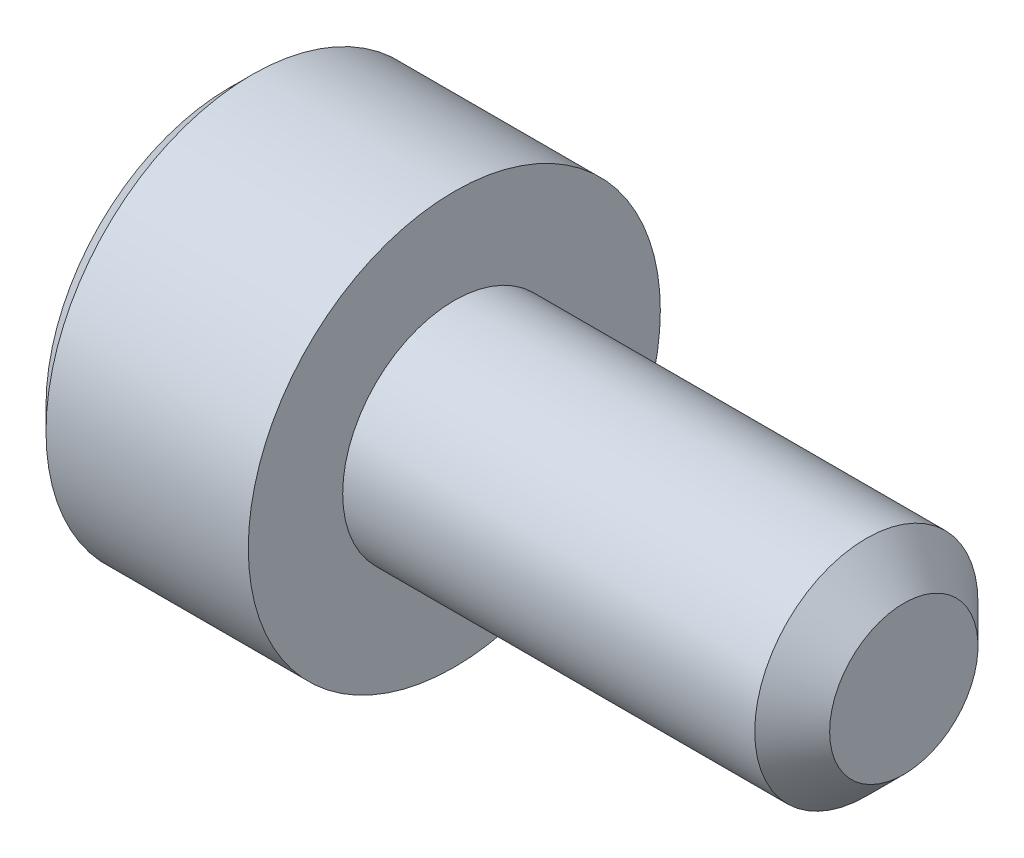
SolidWorks part; units mm, degrees
material "AISI Type 316L stainless steel"
ref_plane "Front Plane" through (0, 0, 0) normal (0, 0, 1) x (1, 0, 0)
ref_plane "Top Plane" through (0, 0, 0) normal (0, 1, 0) x (1, 0, 0)
ref_plane "Right Plane" through (0, 0, 0) normal (1, 0, 0) x (0, 0, -1)
sketch "Sketch1" plane through (0, 0, 0) normal (0, 0, 1) x (1, 0, 0)
  line L0 (-88.7055, 0) -> (96.9812, 0) construction
  line L1 (0, 0) -> (0, 2.75)
  line L2 (0, 2.75) -> (3, 2.75)
  line L4 (9, 0) -> (9, 1.49)
  line L5 (9, 1.49) -> (3, 1.49)
  line L6 (3, 1.49) -> (3, 2.75)
  line L7 (0, 0) -> (9, 0)
  dimension "D1" = 6
  dimension "D2" = 3
  dimension "D3" = 2.75
  dimension "D4" = 1.49
revolve "Revolve1" add sketch "Sketch1" angle 360 about L0
chamfer "Chamfer1" distance 0.5 angle 45 1 edges at (9, 0, 1.49)
chamfer "Chamfer2" distance 0.3 angle 45 1 edges at (0, 0, 2.75)
sketch "Sketch3" plane through (0, 0, 0) normal (1, 0, 0) x (0, 0, -1)
  line L1 (-1.4434, 0) -> (-0.7217, -1.25)
  line L2 (-0.7217, -1.25) -> (0.7217, -1.25)
  line L3 (0.7217, -1.25) -> (1.4434, 0)
  line L4 (1.4434, 0) -> (0.7217, 1.25)
  line L5 (0.7217, 1.25) -> (-0.7217, 1.25)
  line L6 (-0.7217, 1.25) -> (-1.4434, 0)
  circle A0 centre (0, 0) radius 1.25 construction
extrude "Cut-Extrude1" cut sketch "Sketch3" along normal blind 2.5
chamfer "Chamfer3" distance 0.3 angle 45 6 edges at (0, 1.25, 0) (0, 0.625, 1.0825) (0, -0.625, 1.0825) (0, -1.25, 0) (0, -0.625, -1.0825) (0, 0.625, -1.0825)
sketch "Sketch5" plane through (9, 0, 0) normal (1, 0, 0) x (0, 0, -1)
  circle A0 centre (0, 0) radius 1.49
curve "Helix/Spiral1" pitch 0.5 height 20 turns 40
sketch "Sketch8" plane through (0, 0, 0) normal (0, 1, 0) x (1, 0, 0)
  line L0 (9, 1.49) -> (9, 1.1111) construction
  line L1 (9.0625, 1.2194) -> (9.3281, 1.6794)
  line L2 (9.3281, 1.6794) -> (8.6719, 1.6794)
  line L3 (8.6719, 1.6794) -> (8.9375, 1.2194)
  line L4 (9, -0.99) -> (9, 0.99) construction
  circle A0 centre (9, 1.49) radius 0.1894 construction
  arc A1 (9.0625, 1.2194) -> (8.9375, 1.2194) centre (9, 1.2555) cw
  dimension "D2" = 0.0722
  dimension "D1" = 0.3789
sweep "Cut-Sweep1" [suppressed] cut profiles "Sketch8" path "Helix/Spiral1"
equation "\"length\"= 6"
equation "\"D1@Sketch1\"=\"length\""
